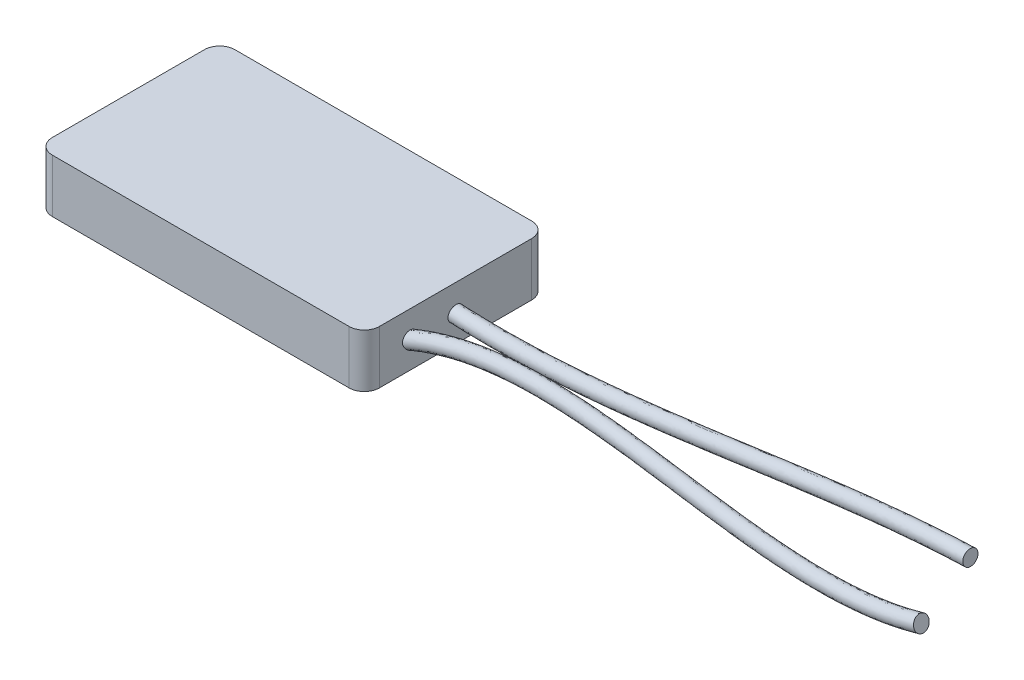
SolidWorks part; units mm, degrees
ref_plane "Front Plane" through (0, 0, 0) normal (0, 0, 1) x (1, 0, 0)
ref_plane "Top Plane" through (0, 0, 0) normal (0, 1, 0) x (1, 0, 0)
ref_plane "Right Plane" through (0, 0, 0) normal (1, 0, 0) x (0, 0, -1)
sketch "Sketch1" plane through (0, 0, 0) normal (0, 1, 0) x (1, 0, 0)
  line L1 (-9.75, -6) -> (9.75, -6)
  line L2 (-10.75, -5) -> (-10.75, 5)
  line L3 (-9.75, 6) -> (9.75, 6)
  line L4 (10.75, -5) -> (10.75, 5)
  line L5 (-10.75, -6) -> (10.75, 6) construction
  line L6 (-10.75, 6) -> (10.75, -6) construction
  arc A0 (-9.75, -6) -> (-10.75, -5) centre (-9.75, -5) cw
  arc A1 (9.75, -6) -> (10.75, -5) centre (9.75, -5) ccw
  arc A2 (9.75, 6) -> (10.75, 5) centre (9.75, 5) cw
  arc A3 (-10.75, 5) -> (-9.75, 6) centre (-9.75, 5) cw
  point P0 (0, 0)
  dimension "D3" = 1
  dimension "D1" = 21.5
  dimension "D2" = 12
extrude "Boss-Extrude1" add sketch "Sketch1" along normal blind 3.5
sketch "Sketch3" plane through (0, 0, 0) normal (0, 0, 1) x (1, 0, 0)
  line L0 (10.75, 3.5) -> (10.75, 0) construction
  spline S0 degree 3 poles (10.75, 1.75) (22.112, 1.2119) (33.2532, 4.3463) (44.5783, 4.762) knots 0 0 0 0 1 1 1 1
  point P2 (0, 0)
sweep "Sweep1" add path "Sketch3" circular profile diameter 1 parameters "D3"=1
ref_plane "Plane1" through (0, 0, 3) normal (0, 0, 1) x (1, 0, 0)
sketch "Sketch18" plane through (0, 0, 3) normal (0, 0, 1) x (1, 0, 0)
  spline S0 degree 3 poles (10.75, 1.75) (21.8142, 6.434) (33.0853, -0.7983) (44.3566, 2.4044) knots 0 0 0 0 1 1 1 1
sweep "Sweep2" add path "Sketch18" circular profile diameter 1 parameters "D3"=1
